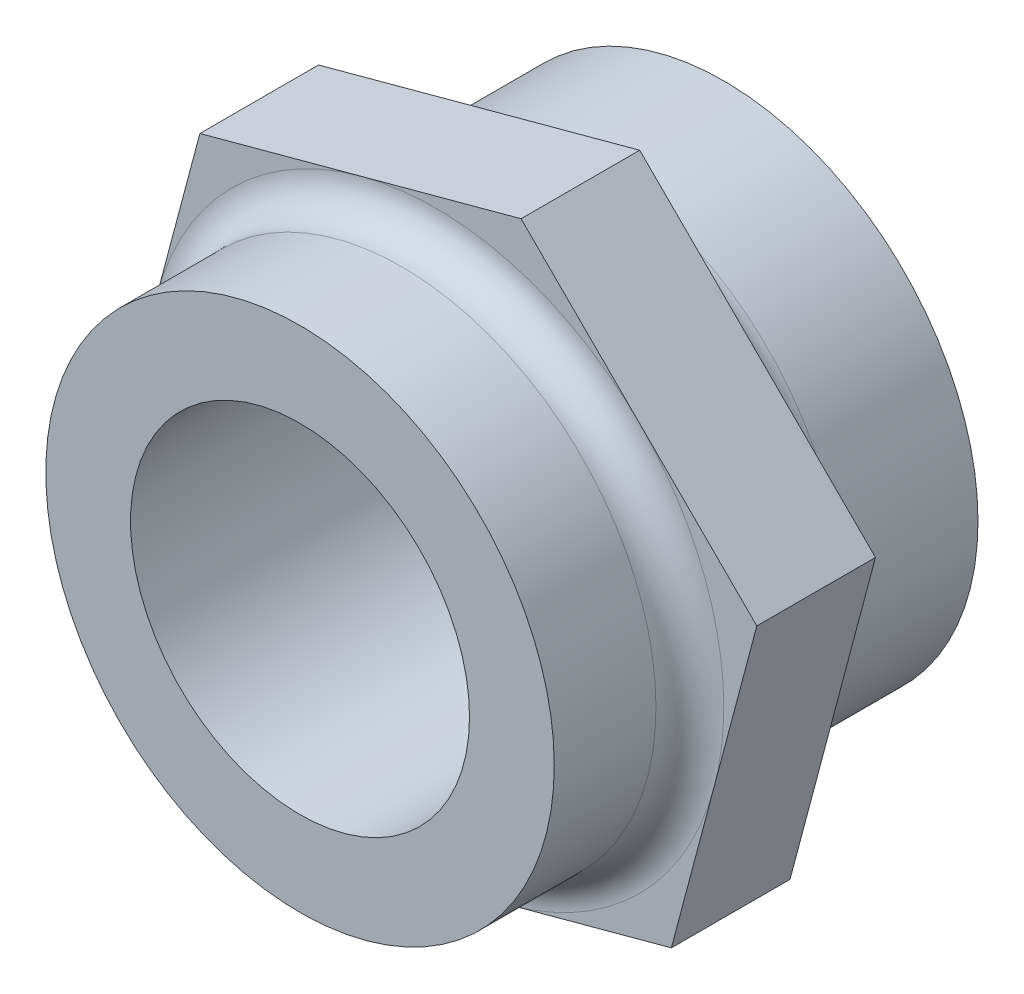
SolidWorks part; units mm, degrees
ref_plane "Front Plane" through (0, 0, 0) normal (0, 0, 1) x (1, 0, 0)
ref_plane "Top Plane" through (0, 0, 0) normal (0, 1, 0) x (1, 0, 0)
ref_plane "Right Plane" through (0, 0, 0) normal (1, 0, 0) x (0, 0, -1)
sketch "Sketch1" plane through (0, 0, 0) normal (0, 0, 1) x (1, 0, 0)
  circle A0 centre (0, 0) radius 10.5
  circle A1 centre (0, 0) radius 15
  dimension "D1" = 21
  dimension "D2" = 30
extrude "Boss-Extrude1" add sketch "Sketch1" along normal blind 25
sketch "Sketch2" plane through (0, 0, 25) normal (0, 0, 1) x (1, 0, 0)
  circle A1 centre (0, 0) radius 10.25
  circle A2 centre (0, 0) radius 15
  circle A3 centre (0, 0) radius 15
  dimension "D2" = 20.5
  dimension "D1" = 0
extrude "Boss-Extrude3" add sketch "Sketch2" against normal blind 15
thread "Thread1" pitch 2 method extrude trim with start face yes trim with end face yes profile "Thread Profile1" start angle 0, offset 5, length 0, pitch 2, diameter 21
ref_plane "Plane1" through (10.5, 0, -5) normal (0, -1, 0) x (1, 0, 0)
sketch "Thread Profile1" plane through (10.5, 0, -5) normal (0, -1, 0) x (1, 0, 0)
  line L0 (0, 0) -> (0, 2) construction
  line L11 (0, 0) -> (0, 1.75)
  line L12 (0, 1.75) -> (-1.0825, 1.125)
  line L13 (-1.0825, 1.125) -> (-1.0825, 0.625)
  line L15 (-1.0825, 0.625) -> (0, 0)
  line L17 (-1.0825, 0.875) -> (0, 0.875) construction
  point P2 (0, 0)
  dimension "Pitch" = 2
  dimension "Profile_Angle" = 60
  dimension "Profile_Land" = 0.5
  dimension "Profile_Height" = 1.0825
sketch "Sketch5" plane through (0, 0, 25) normal (0, 0, 1) x (1, 0, 0)
  circle A0 centre (0, 0) radius 10
  circle A1 centre (0, 0) radius 15
  dimension "D1" = 20
extrude "Boss-Extrude4" add sketch "Sketch5" against normal blind 15
sketch "Sketch6" plane through (0, 0, 25) normal (0, 0, 1) x (1, 0, 0)
  line L1 (-5.0416, -18.9714) -> (13.9089, -13.8519)
  line L2 (13.9089, -13.8519) -> (18.9506, 5.1196)
  line L3 (18.9506, 5.1196) -> (5.0416, 18.9714)
  line L4 (5.0416, 18.9714) -> (-13.9089, 13.8519)
  line L5 (-13.9089, 13.8519) -> (-18.9506, -5.1196)
  line L6 (-18.9506, -5.1196) -> (-5.0416, -18.9714)
  circle A0 centre (0, 0) radius 17 construction
  circle A1 centre (0, 0) radius 15
  dimension "D1" = 17
extrude "Boss-Extrude5" add sketch "Sketch6" against normal blind 15
sketch "Sketch7" plane through (0, 0, 25) normal (0, 0, 1) x (1, 0, 0)
  line L12 (-18.9506, -5.1196) -> (-5.0416, -18.9714)
  line L13 (-5.0416, -18.9714) -> (13.9089, -13.8519)
  line L14 (13.9089, -13.8519) -> (18.9506, 5.1196)
  line L15 (18.9506, 5.1196) -> (5.0416, 18.9714)
  line L16 (5.0416, 18.9714) -> (-13.9089, 13.8519)
  line L17 (-13.9089, 13.8519) -> (-18.9506, -5.1196)
  line L18 (-18.9506, -5.1196) -> (-5.0416, -18.9714)
  line L19 (-5.0416, -18.9714) -> (13.9089, -13.8519)
  line L20 (13.9089, -13.8519) -> (18.9506, 5.1196)
  line L21 (18.9506, 5.1196) -> (5.0416, 18.9714)
  line L22 (5.0416, 18.9714) -> (-13.9089, 13.8519)
  line L23 (-13.9089, 13.8519) -> (-18.9506, -5.1196)
  circle A0 centre (0, 0) radius 15
  dimension "D1" = 30
  dimension "D2" = 0
extrude "Cut-Extrude1" cut sketch "Sketch7" against normal blind 8
fillet "Fillet1" radius 2 2 edges at (15, 0, 10) (15, 0, 17)
equation "\"inner\"=21"
equation "\"D1@Sketch1\"=\"inner\""
equation "\"outer\"=30"
equation "\"D2@Sketch1\"=\"outer\""
equation "\"len\"=25"
equation "\"D1@Boss-Extrude1\"=\"len\""
equation "\"D2@Sketch2\"=\"inner\"-0.5"
equation "\"D1@Boss-Extrude3\"=\"len\"-10"
equation "\"D1@Sketch5\"=\"inner\"-1"
equation "\"D1@Boss-Extrude4\"=\"len\"-10"
equation "\"D1@Sketch6\"=\"outer\"/2+2"
equation "\"D1@Sketch7\"=\"outer\""
